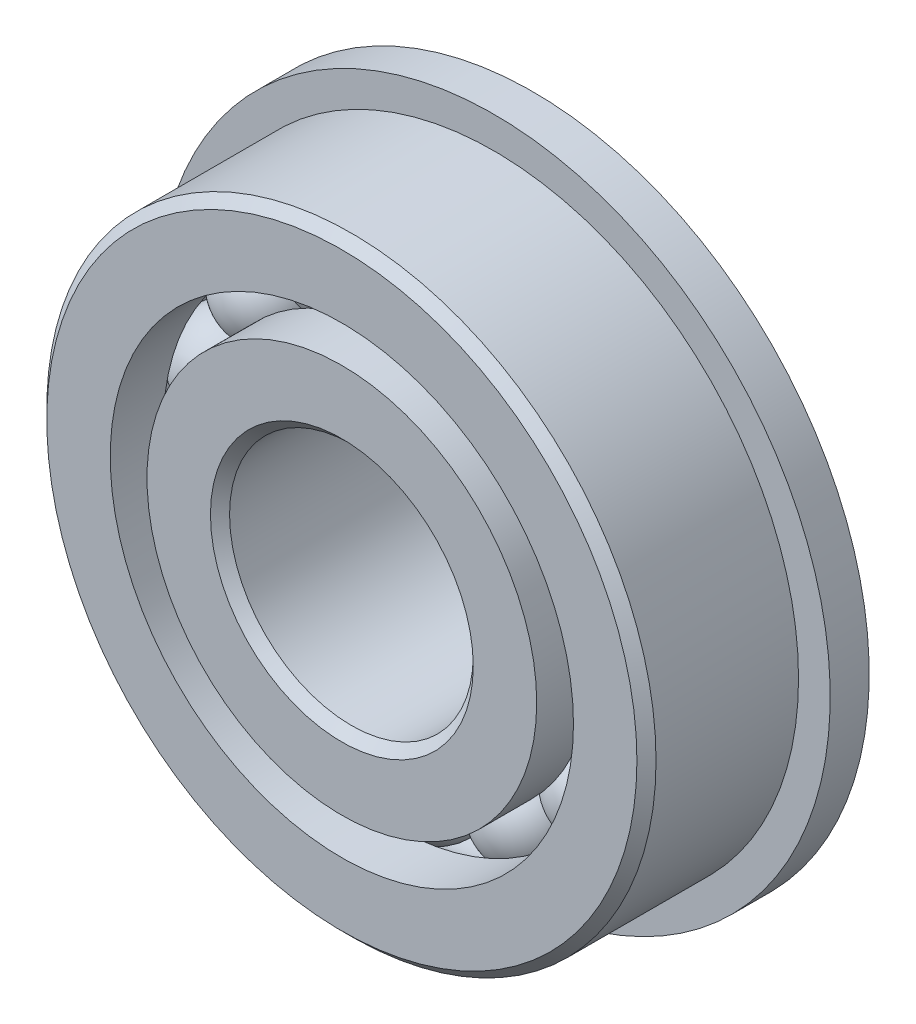
SolidWorks part; units mm, degrees
ref_plane "Front Plane" through (0, 0, 0) normal (0, 0, 1) x (1, 0, 0)
ref_plane "Top Plane" through (0, 0, 0) normal (0, 1, 0) x (1, 0, 0)
ref_plane "Right Plane" through (0, 0, 0) normal (1, 0, 0) x (0, 0, -1)
sketch "Sketch1" plane through (0, 0, 0) normal (1, 0, 0) x (0, 0, -1)
  line L0 (-2.4892, 0) -> (2.4892, 0) construction
  line L1 (0, 7.9375) -> (0, -7.9375) construction
  line L2 (2.2403, 7.9375) -> (-2.2403, 7.9375)
  line L3 (-2.2403, 7.9375) -> (-2.4892, 7.6886)
  line L4 (-2.4892, 7.6886) -> (-2.4892, 6.0352)
  line L5 (-2.4892, 6.0352) -> (-1.1063, 6.0352)
  line L6 (2.4892, 6.0352) -> (1.1063, 6.0352)
  line L7 (2.4892, 7.6886) -> (2.4892, 6.0352)
  line L8 (2.2403, 7.9375) -> (2.4892, 7.6886)
  line L9 (0, 7.9375) -> (0, 5.5563) construction
  line L10 (0, 5.5563) -> (0, 3.175) construction
  arc A0 (-1.1063, 6.0352) -> (1.1063, 6.0352) centre (0, 5.5563) cw
  point P14 (0, 3.175)
  dimension "Width" = 4.9784
  dimension "OD" = 15.875
  dimension "D1" = 45
  dimension "D2" = 0.2489
  dimension "Shaft Dia" = 6.35
  dimension "D3" = 2.2126
  dimension "D4" = 0.479
revolve "Revolve1" add sketch "Sketch1" angle 360 about L0
sketch "Sketch3" plane through (0, 0, 0) normal (1, 0, 0) x (0, 0, -1)
  line L0 (-2.4892, 5.0773) -> (-1.1063, 5.0773)
  line L1 (0, 7.9375) -> (0, -7.9375) construction
  line L2 (-2.4892, 7.6886) -> (-2.4892, 6.0352) construction
  line L3 (-2.4892, 5.0773) -> (-2.4892, 3.4239)
  line L4 (-2.2403, 7.9375) -> (-2.4892, 7.6886) construction
  line L5 (-2.4892, 3.4239) -> (-2.2403, 3.175)
  line L6 (-2.2403, 3.175) -> (2.2403, 3.175)
  line L7 (2.2403, 7.9375) -> (2.2403, -7.9375) construction
  line L8 (2.2403, 3.175) -> (2.4892, 3.4239)
  line L9 (2.4892, -7.6886) -> (2.4892, 7.6886) construction
  line L10 (2.4892, 3.4239) -> (2.4892, 5.0773)
  line L11 (2.4892, 5.0773) -> (1.1063, 5.0773)
  line L13 (2.2403, 7.9375) -> (2.4892, 7.6886) construction
  arc A0 (1.1063, 6.0352) -> (-1.1063, 6.0352) centre (0, 5.5563) ccw construction
  arc A1 (1.1063, 5.0773) -> (-1.1063, 5.0773) centre (0, 5.5562) cw
revolve "Revolve3" add sketch "Sketch3" angle 360 about L0
sketch "Sketch4" plane through (0, 0, 0) normal (1, 0, 0) x (0, 0, -1)
  line L0 (-1.2055, 5.5563) -> (1.2055, 5.5563)
  arc A2 (-1.2055, 5.5563) -> (1.2055, 5.5563) centre (0, 5.5563) cw
  arc A3 (1.1063, 6.0352) -> (-1.1063, 6.0352) centre (0, 5.5563) ccw construction
revolve "Revolve4" add sketch "Sketch4" angle 360 about L0
ref_axis "Axis1" through (0, 0, -2.4892) along (0, 0, 1)
pattern_circular "CirPattern1" count 14 every 25.714 about axis through (0, 0, -2.4892) along (0, 0, 1) of bodies 104
sketch "Sketch5" plane through (0, 0, 0) normal (1, 0, 0) x (0, 0, -1)
  line L0 (-2.4892, 6.0352) -> (-1.1063, 6.0352) construction
  line L1 (-2.3647, 6.0352) -> (-1.2055, 6.0352)
  line L2 (-2.3647, 6.0352) -> (-2.3647, 5.0773)
  line L3 (-2.3647, 5.0773) -> (-1.2055, 5.0773)
  line L4 (-1.2055, 6.0352) -> (-1.2055, 5.0773)
  line L5 (-2.4892, 5.0773) -> (-1.1063, 5.0773) construction
  line L6 (2.4892, 6.0352) -> (1.1063, 6.0352) construction
  line L7 (2.3647, 6.0352) -> (1.2055, 6.0352)
  line L8 (2.3647, 6.0352) -> (2.3647, 5.0773)
  line L9 (2.3647, 5.0773) -> (1.2055, 5.0773)
  line L10 (1.2055, 6.0352) -> (1.2055, 5.0773)
  line L11 (2.4892, 5.0773) -> (1.1063, 5.0773) construction
  line L12 (-2.2403, 7.9375) -> (-2.4892, 7.6886) construction
  point P18 (-2.3647, 7.813)
revolve "Revolve5" [suppressed] add sketch "Sketch5" angle 360 about L0
sketch "Sketch6" plane through (0, 0, 0) normal (1, 0, 0) x (0, 0, -1)
  line L0 (2.4892, 0) -> (-2.4892, 0) construction
  line L1 (2.4892, 6.0352) -> (1.4732, 6.0352)
  line L2 (2.4892, 6.0352) -> (2.4892, 8.763)
  line L3 (2.4892, 8.763) -> (1.4732, 8.763)
  line L4 (1.4732, 6.0352) -> (1.4732, 8.763)
  dimension "Th" = 1.016
  dimension "Flange OD" = 17.526
revolve "Revolve6" add sketch "Sketch6" angle 360 about L0
equation "\"D2@Sketch1\" = \"Width@Sketch1\"*.05"
equation "\"D3@Sketch1\" = \"Width@Sketch1\"/2.25"
equation "\"D4@Sketch1\" = (((\"OD@Sketch1\"-\"Width@Sketch1\")/2)/3.25)/3.5"
equation "\"D2@CirPattern1\" = 360/\"Balls@CirPattern1\""
